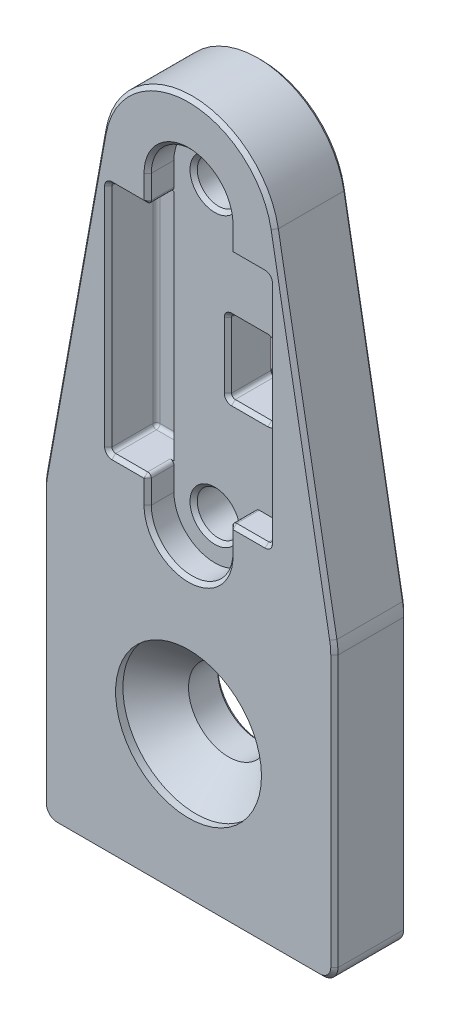
SolidWorks part; units mm, degrees
ref_plane "Front Plane" through (0, 0, 0) normal (0, 0, 1) x (1, 0, 0)
ref_plane "Top Plane" through (0, 0, 0) normal (0, 1, 0) x (1, 0, 0)
ref_plane "Right Plane" through (0, 0, 0) normal (1, 0, 0) x (0, 0, -1)
sketch "Sketch1" plane through (0, 0, 0) normal (0, 0, 1) x (1, 0, 0)
  line L0 (-21.8994, 0) -> (21.4746, 0) construction
  line L1 (0, 20.9985) -> (0, -16.0644) construction
  line L2 (-10, 10) -> (10, 10) construction
  line L3 (-10, 53.5) -> (10, 53.5)
  line L4 (-10, 53.5) -> (-10, -10)
  line L5 (-10, -10) -> (10, -10)
  line L6 (10, 53.5) -> (10, -10)
  line L7 (-10, 53.5) -> (10, -10) construction
  line L8 (-10, -10) -> (10, 53.5) construction
  line L9 (-10, 10) -> (10, -10) construction
  line L10 (-10, 10) -> (-10, -10) construction
  line L11 (-10, 10) -> (10, 53.5) construction
  line L12 (-10, 10) -> (-5.9056, 32.8101)
  line L13 (10, 10) -> (5.9056, 32.8101)
  circle A0 centre (0, 31.75) radius 6
  circle A1 centre (0, 0) radius 2.75
  point P4 (0, 21.75)
  point P12 (0, 0)
  point P13 (0, 31.75)
  dimension "D3" = 12
  dimension "D4" = 5.5
  dimension "D1" = 20
  dimension "D2" = 43.5
extrude "Boss-Extrude1" add sketch "Sketch1" along normal blind 5 contours A0 | A0 L12 L4 L5 L6 L13 A1 region at (0, 7.9884, 0) region at (0, 31.75, 0)
fillet "Fillet1" radius 1 2 edges at (10, -10, 2.5) (-10, -10, 2.5)
fillet "Fillet2" radius 5 2 edges at (10, 10, 2.5) (-10, 10, 2.5)
hole_wizard "CSK for M5 Flat Head Machine Screw1" positions "Sketch3" profile "Sketch4" countersink size "M5" standard "ANSI Metric" end condition through all
sketch "Sketch3" plane through (0, 0, 5) normal (0, 0, 1) x (1, 0, 0)
  point P0 (0, 0)
sketch "Sketch4" plane through (0, 0, 5) normal (1, 0, 0) x (0, -1, 0)
  line L0 (0, 0) -> (0, 5)
  line L1 (0, 5) -> (2.75, 5)
  line L2 (2.75, 5) -> (2.75, 2.75)
  line L3 (2.75, 2.75) -> (5, 0.5)
  line L4 (5, 0.5) -> (5, 0)
  line L6 (5, 0) -> (0, 0)
  line L7 (-2.75, 2.75) -> (-5, 0.5) construction
  line L11 (0, -6.35) -> (0, 107.95) construction
  dimension "Thru Hole Dia." = 5.5
  dimension "Thru Hole Depth" = 5
  dimension "C'Sink Dia." = 10
  dimension "C'Sink Angle" = 90
  dimension "Head Clearance" = 0.5
chamfer "Chamfer1" distance 0.25 angle 45 20 edges at (9.7071, -9.7071, 0) (0, -10, 0) (-9.7071, -9.7071, 0) (10, 0.2774, 0) (9.9803, 9.9982, 0) (-10, 0.2774, 0) (7.9135, 21.6241, 0) (-9.9803, 9.9982, 0) (0, 37.75, 0) (-7.9135, 21.6241, 0) (-9.7071, -9.7071, 5) (0, -10, 5) (-10, 0.2774, 5) (9.7071, -9.7071, 5) (-9.9803, 9.9982, 5) (10, 0.2774, 5) (-7.9135, 21.6241, 5) (9.9803, 9.9982, 5) (0, 37.75, 5) (7.9135, 21.6241, 5)
sketch "Sketch5" plane through (0, 0, 5) normal (0, 0, 1) x (1, 0, 0)
  line L0 (0, 39.621) -> (0, -14.9634) construction
  circle A0 centre (0, 31.75) radius 1.45
  circle A1 centre (0, 12.05) radius 1.45
  arc A2 (5.9056, 32.8101) -> (-5.9056, 32.8101) centre (0, 31.75) ccw construction
  dimension "D2" = 2.9
  dimension "D1" = 19.7
extrude "Cut-Extrude1" cut sketch "Sketch5" against normal up to next
sketch "Sketch6" plane through (0, 0, 5) normal (0, 0, 1) x (1, 0, 0)
  line L0 (0, 31.75) -> (0, 12.05) construction
  line L1 (-2.8394, 21.9) -> (3.3915, 21.9) construction
  line L2 (-2.8, 31.75) -> (-2.8, 29.9)
  line L3 (-5.5, 13.9) -> (5.5, 13.9)
  line L4 (-5.5, 13.9) -> (-5.5, 29.9)
  line L5 (-5.5, 29.9) -> (5.5, 29.9)
  line L6 (5.5, 13.9) -> (5.5, 29.9)
  line L7 (-5.5, 13.9) -> (5.5, 29.9) construction
  line L8 (-5.5, 29.9) -> (5.5, 13.9) construction
  line L9 (2.8, 31.75) -> (2.8, 29.9)
  line L10 (2.8, 12.05) -> (2.8, 13.9)
  line L11 (-2.8, 12.05) -> (-2.8, 13.9)
  circle A0 centre (0, 31.75) radius 2.8
  circle A1 centre (0, 12.05) radius 2.8
  point P6 (0, 21.9)
  point P8 (0, 21.9)
  circle M11 centre (0, 31.75) radius 1.45
  circle M12 centre (0, 12.05) radius 1.45
  line M19 (9.6753, 10.394) -> (5.6595, 32.7659)
  line M21 (-5.6595, 32.7659) -> (-9.6753, 10.394)
  circle M23 centre (0, 0) radius 5
  dimension "D1" = 5.6
  dimension "D2" = 11
  dimension "D3" = 16
extrude "Cut-Extrude2" cut sketch "Sketch6" against normal blind 1.8 contours A0 L5 M11 | A0 L2 L5 | A0 L5 L9 | L5 A0 | A1 L3 L11 | L3 A1 M23 M12 | L3 A1 | A1 L10 L3 | A1 L3 L6 L5 A0 L4 M19 M21 region at (-2.5959, 30.3502, 5) region at (0, 34.4772, 5) region at (0, 21.9, 5) region at (2.5959, 30.3502, 5) region at (0, 29.5139, 5) region at (-2.5959, 13.4498, 5) region at (0, 14.2861, 5) region at (0, 13.8272, 5) region at (2.5959, 13.4498, 5)
sketch "Sketch7" plane through (0, 0, 3.2) normal (0, 0, 1) x (1, 0, 0)
  line L1 (-5.5, 29.9) -> (-2.8, 29.9)
  line L2 (-5.5, 29.9) -> (-5.5, 13.9)
  line L3 (-5.5, 13.9) -> (-2.8, 13.9)
  line L4 (-2.8, 29.9) -> (-2.8, 13.9)
extrude "Cut-Extrude3" cut sketch "Sketch7" against normal blind 1.5
sketch "Sketch8" plane through (0, 0, 3.2) normal (0, 0, 1) x (1, 0, 0)
  line L0 (-5.5, 21.9) -> (5.5, 21.9) construction
  line L1 (-5.5, 29.9) -> (-5.5, 13.9) construction
  line L2 (5.5, 13.9) -> (5.5, 29.9) construction
  line L3 (5.5, 13.9) -> (5.5, 29.9) construction
  line L4 (0.9, 24.4) -> (3.9, 24.4)
  line L5 (0.9, 24.4) -> (0.9, 19.4)
  line L6 (0.9, 19.4) -> (3.9, 19.4)
  line L7 (3.9, 24.4) -> (3.9, 19.4)
  line L8 (0.9, 24.4) -> (3.9, 19.4) construction
  line L9 (0.9, 19.4) -> (3.9, 24.4) construction
  point P6 (2.4, 21.9)
  dimension "D1" = 3
  dimension "D2" = 5
  dimension "D3" = 1.6
extrude "Cut-Extrude4" cut sketch "Sketch8" against normal up to next
fillet "Fillet3" radius 0.25 16 edges at (0.9, 24.4, 1.6) (3.9, 24.4, 1.6) (3.9, 19.4, 1.6) (0.9, 19.4, 1.6) (-4.15, 29.9, 1.7) (-2.8, 21.9, 1.7) (-4.15, 13.9, 1.7) (-5.5, 21.9, 1.7) (-2.8, 29.9, 4.1) (-5.5, 29.9, 3.35) (-5.5, 13.9, 3.35) (-2.8, 13.9, 4.1) (2.8, 13.9, 4.1) (5.5, 13.9, 4.1) (5.5, 29.9, 4.1) (2.8, 29.9, 4.1)
chamfer "Chamfer2" distance 0.25 angle 45 36 edges at (1.45, 12.05, 3.2) (0.9, 21.9, 3.2) (0.9732, 19.4732, 3.2) (0.9732, 24.3268, 3.2) (2.4, 19.4, 3.2) (2.4, 24.4, 3.2) (3.8268, 19.4732, 3.2) (3.8268, 24.3268, 3.2) (3.9, 21.9, 3.2) (1.45, 31.75, 3.2) (2.75, 0, 0) (1.45, 12.05, 0) (3.9, 21.9, 0) (3.8268, 19.4732, 0) (3.8268, 24.3268, 0) (2.4, 19.4, 0) (2.4, 24.4, 0) (0.9732, 19.4732, 0) (0.9732, 24.3268, 0) (0.9, 21.9, 0) (1.45, 31.75, 0) (0, 9.25, 5) (2.8, 12.85, 5) (-2.8, 12.85, 5) (2.8732, 13.8268, 5) (-2.8732, 13.8268, 5) (4.15, 13.9, 5) (5.4268, 13.9732, 5) (5.5, 21.9, 5) (5.4268, 29.8268, 5) (4.15, 29.9, 5) (2.8732, 29.9732, 5) (-2.8732, 29.9732, 5) (2.8, 30.95, 5) (-2.8, 30.95, 5) (0, 34.55, 5)
